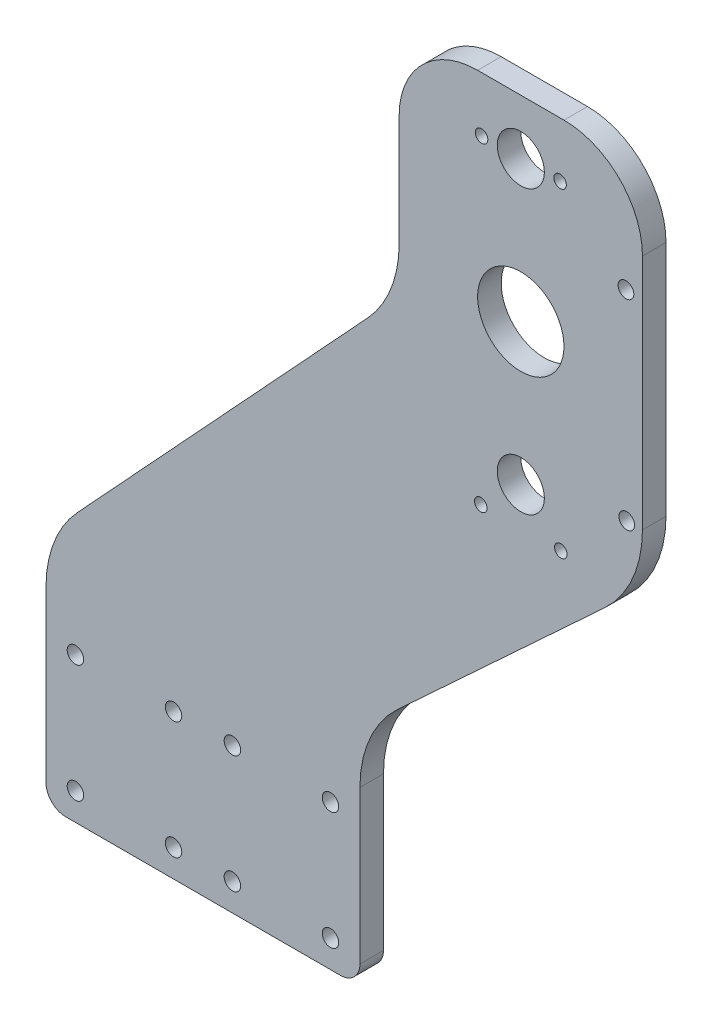
SolidWorks part; units mm, degrees
ref_plane "Front Plane" through (0, 0, 0) normal (0, 0, 1) x (1, 0, 0)
ref_plane "Top Plane" through (0, 0, 0) normal (0, 1, 0) x (1, 0, 0)
ref_plane "Right Plane" through (0, 0, 0) normal (1, 0, 0) x (0, 0, -1)
sketch "Sketch1" plane through (0, 0, 0) normal (0, 0, 1) x (1, 0, 0)
  line L0 (-23.4262, -99.1975) -> (-23.4262, -15.4242) construction
  line L1 (-58.4262, -99.1975) -> (11.5738, -99.1975)
  line L2 (-63.4262, -94.1975) -> (-63.4262, -50.9492)
  line L3 (-63.4262, -94.1975) -> (-23.4262, -94.1975) construction
  line L4 (16.5738, -94.1975) -> (16.5738, -55.2061)
  line L5 (46.5738, 118.0524) -> (68.5738, 118.0524)
  line L6 (26.5738, 98.0524) -> (26.5738, 69.804)
  line L7 (57.5738, 118.0524) -> (57.5738, 32.1124) construction
  line L8 (88.5738, 98.0524) -> (88.5738, 37.6266)
  line L9 (-43.4262, -77.1975) -> (-43.4262, -94.1975) construction
  line L10 (-55.9262, -62.1975) -> (-30.9262, -62.1975) construction
  line L11 (18.5918, 49.4274) -> (-55.4443, -30.5726)
  line L12 (78.945, 15.6036) -> (26.2025, -33.1831)
  line L13 (-55.9262, -62.1975) -> (-55.9262, -92.1975) construction
  line L14 (-55.9262, -92.1975) -> (-30.9262, -92.1975) construction
  line L15 (-30.9262, -62.1975) -> (-30.9262, -92.1975) construction
  line L16 (-55.9262, -62.1975) -> (-30.9262, -92.1975) construction
  line L17 (-55.9262, -92.1975) -> (-30.9262, -62.1975) construction
  line L18 (57.5738, 104.0524) -> (57.5738, 32.1124) construction
  arc A0 (78.945, 15.6036) -> (88.5738, 37.6266) centre (58.5738, 37.6266) ccw
  arc A1 (18.5918, 49.4274) -> (26.5738, 69.804) centre (-3.4262, 69.804) ccw
  arc A2 (16.5738, -55.2061) -> (26.2025, -33.1831) centre (46.5738, -55.2061) cw
  arc A3 (-63.4262, -50.9492) -> (-55.4443, -30.5726) centre (-33.4262, -50.9492) cw
  arc A4 (88.5738, 98.0524) -> (68.5738, 118.0524) centre (68.5738, 98.0524) ccw
  arc A5 (46.5738, 118.0524) -> (26.5738, 98.0524) centre (46.5738, 98.0524) ccw
  arc A6 (16.5738, -94.1975) -> (11.5738, -99.1975) centre (11.5738, -94.1975) cw
  arc A7 (-58.4262, -99.1975) -> (-63.4262, -94.1975) centre (-58.4262, -94.1975) cw
  circle A8 centre (-55.9262, -62.1975) radius 2.1
  circle A9 centre (-30.9262, -62.1975) radius 2.1
  circle A10 centre (-30.9262, -92.1975) radius 2.1
  circle A11 centre (-55.9262, -92.1975) radius 2.1
  circle A12 centre (9.0738, -92.1975) radius 2.1
  circle A13 centre (-15.9262, -92.1975) radius 2.1
  circle A14 centre (-15.9262, -62.1975) radius 2.1
  circle A15 centre (9.0738, -62.1975) radius 2.1
  circle A16 centre (57.5738, 104.0524) radius 6
  circle A17 centre (57.5738, 32.1124) radius 6
  circle A18 centre (57.5738, 68.0824) radius 11
  circle A19 centre (84.5738, 37.6266) radius 2
  circle A20 centre (84.3759, 88.5283) radius 2
  circle A21 centre (47.5738, 104.0524) radius 1.6
  circle A22 centre (47.3759, 22.5883) radius 1.6
  circle A23 centre (67.5738, 104.0524) radius 1.6
  circle A24 centre (67.7716, 22.5883) radius 1.6
  point P0 (0, 0)
  point P1 (57.5738, 82.2289)
  point P15 (26.5738, 58.0524)
  point P20 (-63.4262, -39.1975)
  point P23 (88.5738, 118.0524)
  point P26 (26.5738, 118.0524)
  point P29 (16.5738, -99.1975)
  point P32 (-63.4262, -99.1975)
  point P35 (-43.4262, -77.1975)
  dimension "D5" = 30
  dimension "D6" = 20
  dimension "D7" = 5
  dimension "D14" = 71.94
  dimension "D12" = 4
  dimension "D16" = 10
  dimension "D1" = 80
  dimension "D2" = 22
  dimension "D3" = 90
  dimension "D4" = 60
  dimension "D8" = 25
  dimension "D9" = 60
  dimension "D10" = 22
  dimension "D11" = 80
  dimension "D13" = 30
  dimension "D15" = 14
extrude "Boss-Extrude1" add sketch "Sketch1" along normal blind 6
